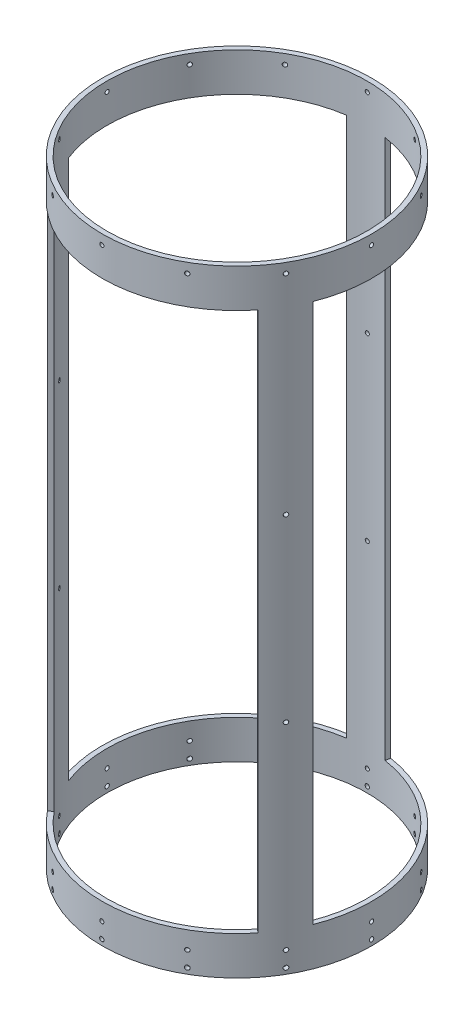
SolidWorks part; units mm, degrees
material "6061-T6 (SS)"
ref_plane "Front Plane" through (0, 0, 0) normal (0, 0, 1) x (1, 0, 0)
ref_plane "Top Plane" through (0, 0, 0) normal (0, 1, 0) x (1, 0, 0)
ref_plane "Right Plane" through (0, 0, 0) normal (1, 0, 0) x (0, 0, -1)
sketch "Sketch1" plane through (0, 0, 0) normal (0, 1, 0) x (1, 0, 0)
  circle A0 centre (0, 0) radius 88.9
  circle A1 centre (0, 0) radius 85.725
  dimension "D1" = 177.8
  dimension "D2" = 171.45
extrude "Boss-Extrude1" add sketch "Sketch1" along normal mid plane 406.4
sketch "Sketch6" plane through (0, -203.2, 0) normal (0, -1, 0) x (-1, 0, 0)
  line L0 (82.7901, -32.3885) -> (79.8333, -31.2317)
  line L1 (13.1222, 87.9262) -> (12.6536, 84.786)
  line L2 (0, 0) -> (0, 85.725) construction
  line L3 (-97.8543, 0) -> (97.8543, 0) construction
  line L4 (0, 0) -> (12.6536, 84.786) construction
  arc A0 (13.1222, 87.9262) -> (82.7901, -32.3885) centre (0, 0) cw
  circle A1 centre (0, 0) radius 88.9 construction
  arc A2 (12.6536, 84.786) -> (79.8333, -31.2317) centre (0, 0) cw
  circle A3 centre (0, 0) radius 85.725 construction
  arc A4 (0, 85.725) -> (12.6536, 84.786) centre (0, 0) cw construction
  dimension "D1" = 153.924
  dimension "D2" = 12.7
extrude "Cut-Extrude5" cut sketch "Sketch6" against normal blind 355.6 from offset 25.4 offset against normal yes
pattern_circular "CirPattern5" count 3 over 360 about axis through (0, -203.2, 0) along (0, 1, 0) of "Cut-Extrude5"
ref_plane "Plane1" through (0, 0, -88.9) normal (0, 0, -1) x (-1, 0, 0)
sketch "Sketch3" plane through (0, 0, 0) normal (0, 0, -1) x (-1, 0, 0)
  line L1 (-88.9, -203.2) -> (88.9, -203.2) construction
  line L3 (-12.8692, 177.8) -> (-12.8692, -177.8) construction
  circle A0 centre (-0.1692, -199.39) radius 1.4351
  circle A1 centre (-0.1692, -189.23) radius 1.3525
  dimension "D1" = 3.81
  dimension "D2" = 2.8702
  dimension "D3" = 2.7051
  dimension "D4" = 12.7
  dimension "D5" = 10.16
extrude "Cut-Extrude2" cut sketch "Sketch3" along normal up to surface (88.891 mm away) up to face at (-0.0918, 0, 72.1578)
pattern_circular "CirPattern2" count 12 over 360 about axis through (0, 203.2, 0) along (0, -1, 0) of "Cut-Extrude2" reverse direction yes
sketch "Sketch4" plane through (0, 0, -88.9) normal (0, 0, -1) x (-1, 0, 0)
  line L1 (88.9, 203.2) -> (-88.9, 203.2) construction
  circle A0 centre (-0.1692, 196.85) radius 1.3525
  dimension "D1" = 2.7051
  dimension "D2" = 6.35
extrude "Cut-Extrude3" cut sketch "Sketch4" against normal blind 15.24
pattern_circular "CirPattern3" count 12 over 360 about axis through (0, 203.2, 0) along (0, 1, 0) of "Cut-Extrude3"
ref_plane "Plane2" through (0, 0, 88.9) normal (0, 0, 1) x (1, 0, 0)
sketch "Sketch5" plane through (0, 0, 88.9) normal (0, 0, 1) x (1, 0, 0)
  line L0 (-88.9, 177.8) -> (-13.1222, 177.8) construction
  line L1 (88.9, -177.8) -> (13.3458, -177.8) construction
  circle A0 centre (0.1692, 59.2667) radius 1.3526
  circle A1 centre (0.1692, -59.2667) radius 1.3526
  dimension "D1" = 118.5333
  dimension "D2" = 118.5333
  dimension "D3" = 2.7051
  dimension "D4" = 2.7051
extrude "Cut-Extrude4" cut sketch "Sketch5" against normal up to surface (177.787 mm away) up to face at (-77.2806, 196.2438, -43.9383)
pattern_circular "CirPattern4" count 3 over 360 about axis through (0, 203.2, 0) along (0, -1, 0) of "Cut-Extrude4"
